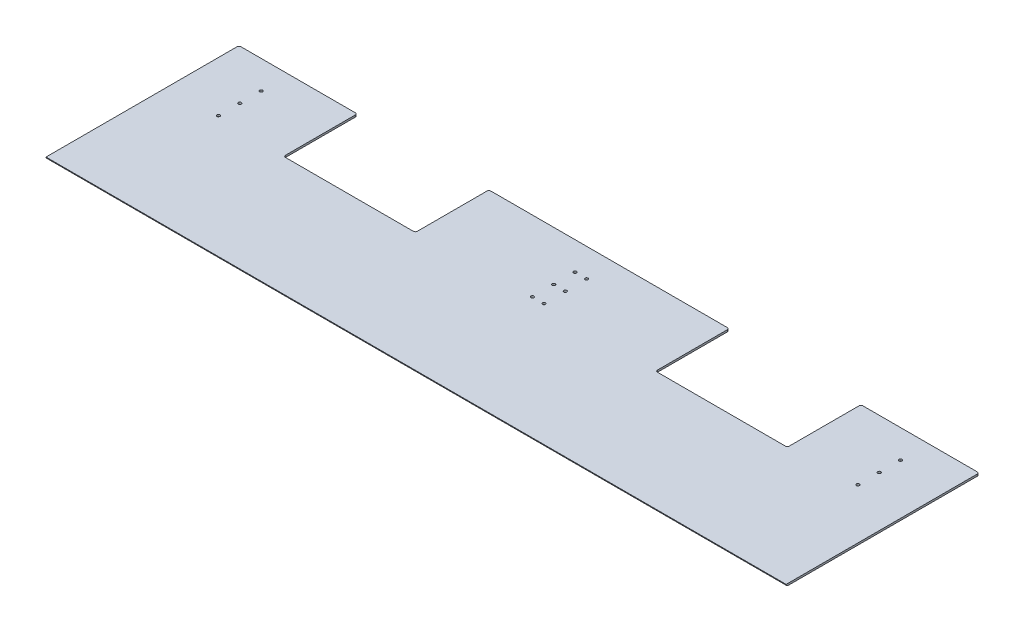
SolidWorks part; units mm, degrees
material "PE High Density"
ref_plane "Front Plane" through (0, 0, 0) normal (0, 0, 1) x (1, 0, 0)
ref_plane "Top Plane" through (0, 0, 0) normal (0, 1, 0) x (1, 0, 0)
ref_plane "Right Plane" through (0, 0, 0) normal (1, 0, 0) x (0, 0, -1)
sketch "Sketch1" plane through (0, 0, 0) normal (0, 1, 0) x (1, 0, 0)
  line L1 (0, 0) -> (1212.85, 0)
  line L2 (0, 0) -> (0, 316.23)
  line L3 (0, 316.23) -> (1212.85, 316.23)
  line L4 (1212.85, 0) -> (1212.85, 316.23)
  dimension "D1" = 1212.85
  dimension "D2" = 316.23
extrude "Boss-Extrude1" add sketch "Sketch1" along normal blind 3.175
fillet "Fillet1" radius 3.175 1 edges at (606.425, 0, 0)
hole_wizard "#10 Clearance Hole1" [suppressed] positions "Sketch2" profile "Sketch3" hole size "#10" standard "ANSI Inch"
sketch "Sketch2" plane through (0, 3.175, 0) normal (0, 1, 0) x (1, 0, 0)
  line L2 (606.425, 316.23) -> (606.425, 0) construction
  line L3 (1212.85, 316.23) -> (0, 316.23) construction
  line L6 (0, 316.23) -> (0, 0) construction
  line L7 (0, 0) -> (1212.85, 0) construction
  line L8 (0, 316.23) -> (0, 0) construction
  line L9 (1212.85, 0) -> (1212.85, 316.23) construction
  point P0 (152.4, 287.1887)
  point P7 (622.3, 287.1887)
  point P8 (1136.65, 287.1887)
  point P9 (622.3, 217.3387)
  point P10 (1136.65, 217.3387)
  point P11 (622.3, 147.4887)
  point P12 (1136.65, 147.4887)
  point P13 (152.4, 217.3387)
  point P14 (152.4, 147.4887)
  dimension "D1" = 69.85
  dimension "D5" = 147.4887
  dimension "D6" = 152.4
  dimension "D7" = 69.85
  dimension "D8" = 29.0413
  dimension "D2" = 622.3
  dimension "D3" = 76.2
sketch "Sketch3" plane through (152.4, 3.175, -287.1887) normal (1, 0, 0) x (0, 0, 1)
  line L0 (0, 0) -> (0, 3.175)
  line L1 (0, 3.175) -> (2.5527, 3.175)
  line L2 (2.5527, 3.175) -> (2.5527, 0)
  line L5 (2.5527, 0) -> (0, 0)
  line L11 (0, -6.35) -> (0, 107.95) construction
  dimension "Thru Hole Dia." = 5.1054
  dimension "Thru Hole Depth" = 3.175
sketch "Sketch4" plane through (0, 3.175, 0) normal (0, 1, 0) x (1, 0, 0)
  line L0 (1212.85, 316.23) -> (0, 316.23) construction
  line L1 (193.675, 316.23) -> (409.575, 316.23)
  line L2 (193.675, 316.23) -> (193.675, 195.58)
  line L3 (193.675, 195.58) -> (409.575, 195.58)
  line L4 (409.575, 316.23) -> (409.575, 195.58)
  line L5 (606.425, 316.23) -> (606.425, 0) construction
  line L6 (0, 0) -> (1212.85, 0) construction
  line L7 (803.275, 316.23) -> (803.275, 195.58)
  line L8 (1019.175, 195.58) -> (803.275, 195.58)
  line L9 (1019.175, 316.23) -> (1019.175, 195.58)
  line L10 (1019.175, 316.23) -> (803.275, 316.23)
  line L11 (301.625, 316.23) -> (301.625, 195.58) construction
  dimension "D1" = 215.9
  dimension "D2" = 120.65
  dimension "D3" = 304.8
extrude "Cut-Extrude1" cut sketch "Sketch4" against normal through all
fillet "Fillet2" radius 3.175 10 edges at (409.575, 1.5875, -195.58) (409.575, 1.5875, -316.23) (803.275, 1.5875, -316.23) (803.275, 1.5875, -195.58) (1019.175, 1.5875, -195.58) (1019.175, 1.5875, -316.23) (1212.85, 1.5875, -316.23) (193.675, 1.5875, -316.23) (193.675, 1.5875, -195.58) (0, 1.5875, -316.23)
hole_wizard "#10 (0.1935) Diameter Hole1" positions "Sketch5" profile "Sketch6" hole size "#10" standard "ANSI Inch" end condition through all
sketch "Sketch5" plane through (0, 3.175, 0) normal (0, 1, 0) x (1, 0, 0)
  line L0 (606.425, 0) -> (606.425, 316.23) construction
  line L1 (0, 0) -> (1212.85, 0) construction
  line L2 (800.1, 316.23) -> (412.75, 316.23) construction
  point P0 (82.55, 200.1012)
  point P2 (82.55, 235.0262)
  point P4 (82.55, 269.9512)
  point P6 (596.9, 200.1012)
  point P8 (596.9, 235.0262)
  point P10 (596.9, 269.9512)
  point P20 (615.95, 269.9512)
  point P21 (615.95, 235.0262)
  point P22 (615.95, 200.1012)
  point P23 (1130.3, 269.9512)
  point P24 (1130.3, 235.0262)
  point P25 (1130.3, 200.1012)
  dimension "D1" = 200.1012
  dimension "D2" = 34.925
  dimension "D3" = 34.925
  dimension "D4" = 9.525
  dimension "D5" = 514.35
sketch "Sketch6" plane through (82.55, 3.175, -200.1012) normal (1, 0, 0) x (0, 0, 1)
  line L0 (0, 0) -> (0, 3.175)
  line L1 (0, 3.175) -> (2.4574, 3.175)
  line L2 (2.4574, 3.175) -> (2.4574, 0)
  line L5 (2.4574, 0) -> (0, 0)
  line L11 (0, -6.35) -> (0, 107.95) construction
  dimension "Thru Hole Dia." = 4.9149
  dimension "Thru Hole Depth" = 3.175
hole_wizard "1/4 (0.25) Diameter Hole1" [suppressed] positions "Sketch7" profile "Sketch8" hole size "1/4" standard "ANSI Inch"
sketch "Sketch7" plane through (0, 3.175, 0) normal (0, 1, 0) x (1, 0, 0)
  line L0 (606.425, 0) -> (606.425, 316.23) construction
  line L1 (0, 0) -> (1212.85, 0) construction
  line L2 (800.1, 316.23) -> (412.75, 316.23) construction
  line L4 (149.225, 150.3997) -> (1063.625, 150.3997) construction
  line L5 (149.225, 150.3997) -> (149.225, 122.6502) construction
  line L6 (149.225, 122.6502) -> (1063.625, 122.6502) construction
  line L7 (1063.625, 150.3997) -> (1063.625, 122.6502) construction
  line L8 (149.225, 136.525) -> (1063.625, 136.525) construction
  point P0 (193.675, 155.575)
  point P2 (193.675, 117.475)
  point P4 (428.625, 155.575)
  point P6 (428.625, 117.475)
  point P20 (784.225, 117.475)
  point P21 (784.225, 155.575)
  point P22 (1019.175, 117.475)
  point P23 (1019.175, 155.575)
  point P164 (606.425, 122.6502)
  dimension "D1" = 355.6
  dimension "D2" = 38.1
  dimension "D3" = 117.475
  dimension "D4" = 914.4
  dimension "D5" = 27.7495
  dimension "D6" = 412.75
sketch "Sketch8" plane through (193.675, 3.175, -155.575) normal (1, 0, 0) x (0, 0, 1)
  line L0 (0, 0) -> (0, 3.175)
  line L1 (0, 3.175) -> (3.175, 3.175)
  line L2 (3.175, 3.175) -> (3.175, 0)
  line L5 (3.175, 0) -> (0, 0)
  line L11 (0, -6.35) -> (0, 107.95) construction
  dimension "Thru Hole Dia." = 6.35
  dimension "Thru Hole Depth" = 3.175
